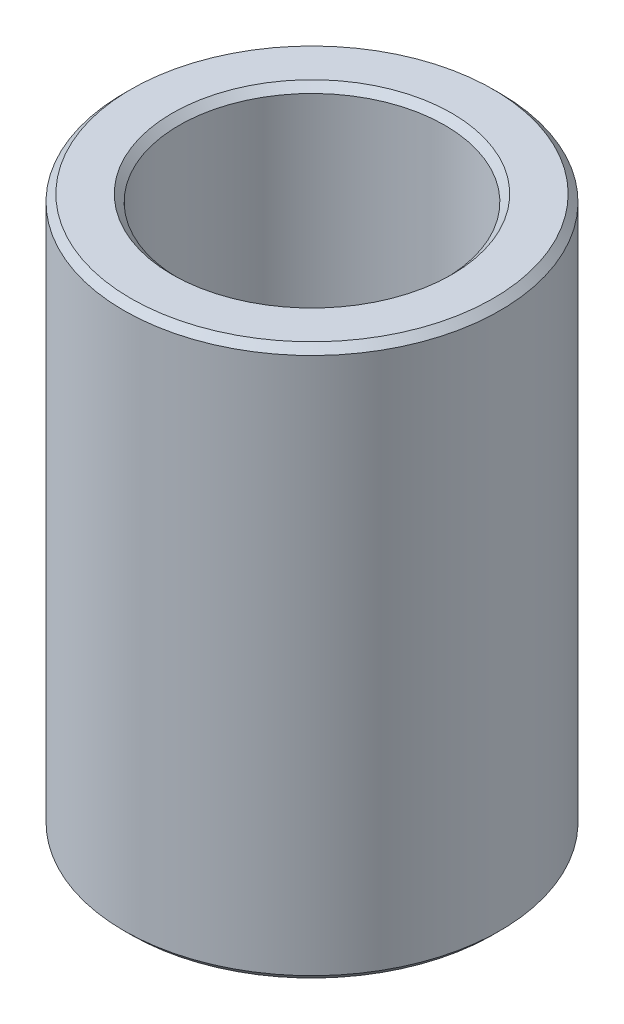
SolidWorks part; units mm, degrees
ref_plane "Front Plane" through (0, 0, 0) normal (0, 0, 1) x (1, 0, 0)
ref_plane "Top Plane" through (0, 0, 0) normal (0, 1, 0) x (1, 0, 0)
ref_plane "Right Plane" through (0, 0, 0) normal (1, 0, 0) x (0, 0, -1)
sketch "Sketch1" plane through (0, 0, 0) normal (0, 1, 0) x (1, 0, 0)
  circle A0 centre (0, 0) radius 47.5
  dimension "SLEEVE_OD" = 95
extrude "Boss-Extrude1" add sketch "Sketch1" along normal blind 139.1387
sketch "Sketch2" plane through (0, 0, 0) normal (0, 1, 0) x (1, 0, 0)
  circle A0 centre (0, 0) radius 33.5501
  dimension "BORE_D" = 67.1002
extrude "Cut-Extrude1" cut sketch "Sketch2" along normal through all
chamfer "Chamfer1" distance 1.7597 angle 45 4 edges at (0, 139.1387, 33.5501) (0, 0, 33.5501) (0, 0, 47.5) (0, 139.1387, 47.5)
